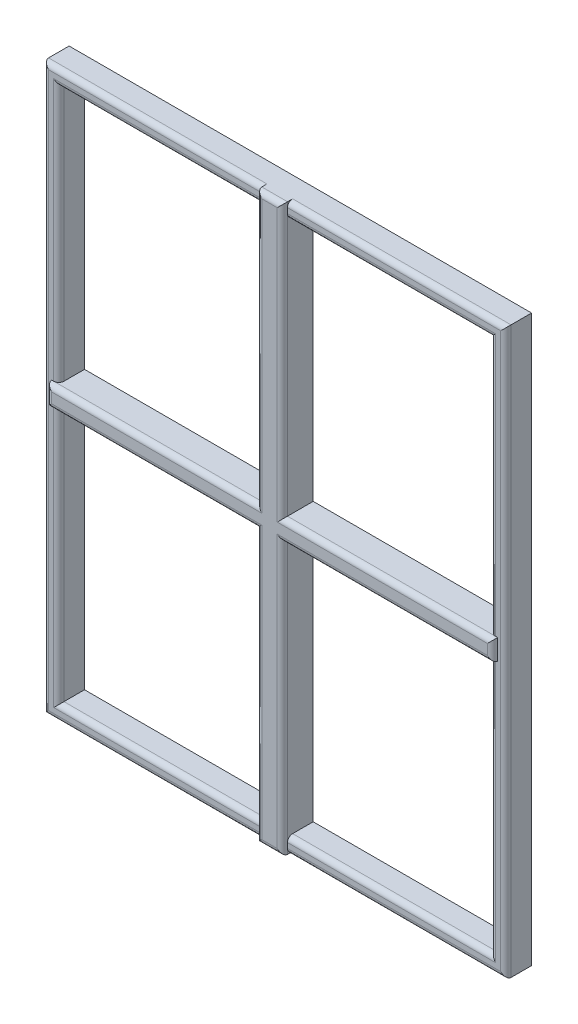
SolidWorks part; units mm, degrees
ref_plane "Front Plane" through (0, 0, 0) normal (0, 0, 1) x (1, 0, 0)
ref_plane "Top Plane" through (0, 0, 0) normal (0, 1, 0) x (1, 0, 0)
ref_plane "Right Plane" through (0, 0, 0) normal (1, 0, 0) x (0, 0, -1)
sketch "Sketch1" plane through (0, 0, 0) normal (0, 0, 1) x (1, 0, 0)
  line L0 (-870, 30) -> (-870, 1070)
  line L1 (0, 0) -> (-900, 0)
  line L2 (0, 0) -> (0, 1100)
  line L3 (0, 1100) -> (-900, 1100)
  line L4 (-900, 0) -> (-900, 1100)
  line L5 (-30, 1070) -> (-870, 1070)
  line L6 (-30, 30) -> (-30, 1070)
  line L7 (-30, 30) -> (-870, 30)
  dimension "D1" = 900
  dimension "D2" = 1100
  dimension "D3" = 30
extrude "Boss-Extrude1" add sketch "Sketch1" along normal blind 50
fillet "Fillet1" radius 10 8 edges at (-450, 1070, 50) (-870, 550, 50) (-450, 30, 50) (-30, 550, 50) (-450, 0, 50) (-900, 550, 50) (-450, 1100, 50) (0, 550, 50)
sketch "Sketch2" plane through (0, 0, 0) normal (0, 0, 1) x (1, 0, 0)
  line L0 (-450, 1100) -> (-450, 0) construction
  line L1 (-900, 1100) -> (0, 1100) construction
  line L2 (0, 0) -> (-900, 0) construction
  line L3 (0, 550) -> (-900, 550) construction
  line L4 (0, 1100) -> (0, 0) construction
  line L5 (-900, 0) -> (-900, 1100) construction
  line L6 (0, 1100) -> (-900, 1100) construction
  line L7 (-475, 1100) -> (-425, 1100)
  line L8 (-475, 1100) -> (-475, 0)
  line L9 (-475, 0) -> (-425, 0)
  line L10 (-425, 1100) -> (-425, 0)
  line L11 (-880, 20) -> (-880, 1080) construction
  line L12 (-16, 570) -> (-884, 570)
  line L13 (-16, 570) -> (-16, 530)
  line L14 (-16, 530) -> (-884, 530)
  line L15 (-884, 570) -> (-884, 530)
  line L16 (-20, 1080) -> (-20, 20) construction
  line L18 (-1580, 1580) -> (-20, 1580)
  line L19 (-1580, 1580) -> (-1580, 20)
  line L20 (-1580, 20) -> (-20, 20)
  line L21 (-20, 1580) -> (-20, 20)
  dimension "D1" = 4
  dimension "D2" = 4
  dimension "D3" = 4
  dimension "D4" = 40
  dimension "D5" = 50
  dimension "D6" = 4
extrude "Boss-Extrude2" add sketch "Sketch2" along normal blind 60 contours L10 L9 L8 L7 | L12 L15 L14 L13
fillet "Fillet2" radius 10 12 edges at (-450, 0, 60) (-475, 265, 60) (-679.5, 530, 60) (-884, 550, 60) (-679.5, 570, 60) (-475, 835, 60) (-450, 1100, 60) (-425, 835, 60) (-220.5, 570, 60) (-16, 550, 60) (-220.5, 530, 60) (-425, 265, 60)
ref_plane "Plane1" through (-475, 1080, 50) normal (1, 0, 0) x (0, 0, -1)
sketch "Sketch3" plane through (-475, 1080, 50) normal (1, 0, 0) x (0, 0, -1)
sketch "Sketch4" plane through (0, 0, 0) normal (0, 0, 1) x (1, 0, 0)
  line L1 (-1580, 1580) -> (-20, 1580)
  line L2 (-1580, 1580) -> (-1580, 20)
  line L3 (-1580, 20) -> (-20, 20)
  line L4 (-20, 1580) -> (-20, 20)
